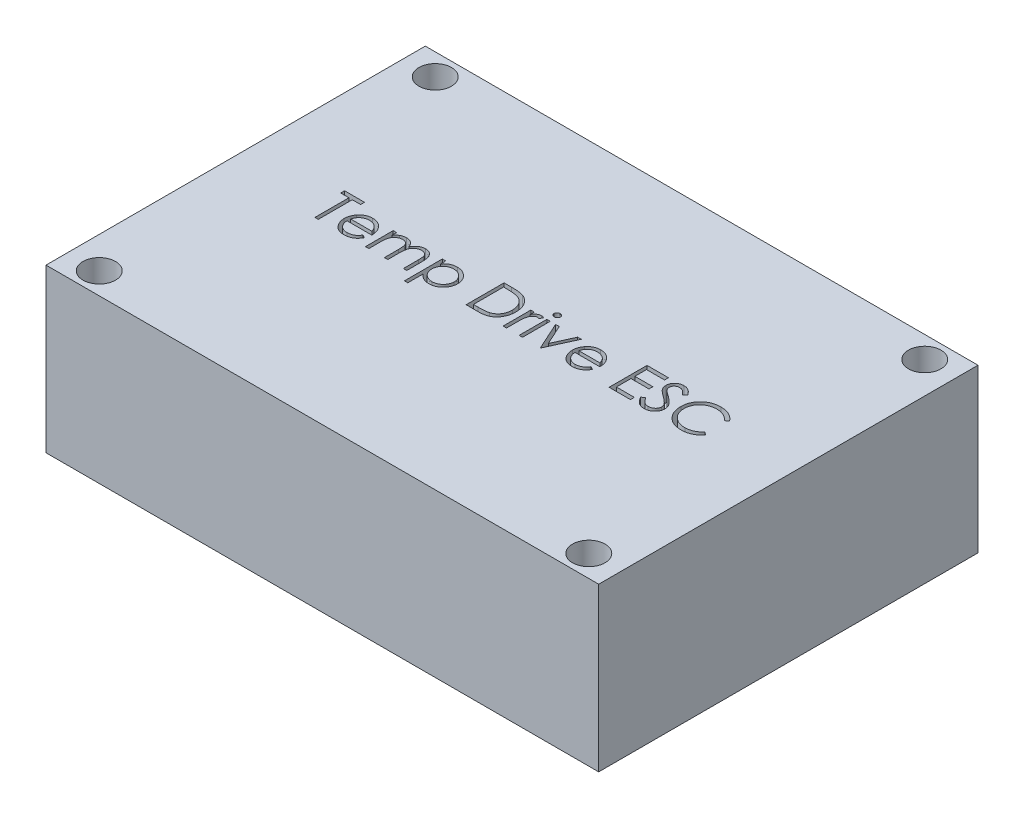
SolidWorks part; units mm, degrees
ref_plane "Front Plane" through (0, 0, 0) normal (0, 0, 1) x (1, 0, 0)
ref_plane "Top Plane" through (0, 0, 0) normal (0, 1, 0) x (1, 0, 0)
ref_plane "Right Plane" through (0, 0, 0) normal (1, 0, 0) x (0, 0, -1)
sketch "Sketch1" plane through (0, 0, 0) normal (0, 1, 0) x (1, 0, 0)
  line L0 (-22.5857, 15.5) -> (-22.5857, -15.5) construction
  line L1 (-25.5, -17.5) -> (25.5, -17.5)
  line L2 (-25.5, -17.5) -> (-25.5, 17.5)
  line L3 (-25.5, 17.5) -> (25.5, 17.5)
  line L4 (25.5, -17.5) -> (25.5, 17.5)
  line L5 (-25.5, -17.5) -> (25.5, 17.5) construction
  line L6 (-25.5, 17.5) -> (25.5, -17.5) construction
  line L7 (-22.5857, -15.5) -> (22.5857, -15.5) construction
  line L8 (22.5857, -15.5) -> (22.5857, 15.5) construction
  line L9 (22.5857, 15.5) -> (-22.5857, 15.5) construction
  circle A0 centre (-22.5857, 15.5) radius 1.5
  circle A1 centre (22.5857, 15.5) radius 1.5
  circle A2 centre (22.5857, -15.5) radius 1.5
  circle A3 centre (-22.5857, -15.5) radius 1.5
  point P0 (0, 0)
  dimension "D3" = 3
  dimension "D4" = 3
  dimension "D5" = 3
  dimension "D6" = 3
  dimension "D1" = 51
  dimension "D2" = 35
  dimension "D7" = 2
  dimension "D8" = 2
  dimension "D9" = 2
  dimension "D10" = 2
  dimension "D11" = 45.1714
  dimension "D12" = 31
extrude "Boss-Extrude1" add sketch "Sketch1" along normal blind 15
sketch "Sketch2" plane through (0, 15, 0) normal (0, 1, 0) x (1, 0, 0)
  text T0 "Temp Drive ESC"
extrude "Cut-Extrude1" cut sketch "Sketch2" against normal blind 1.4
